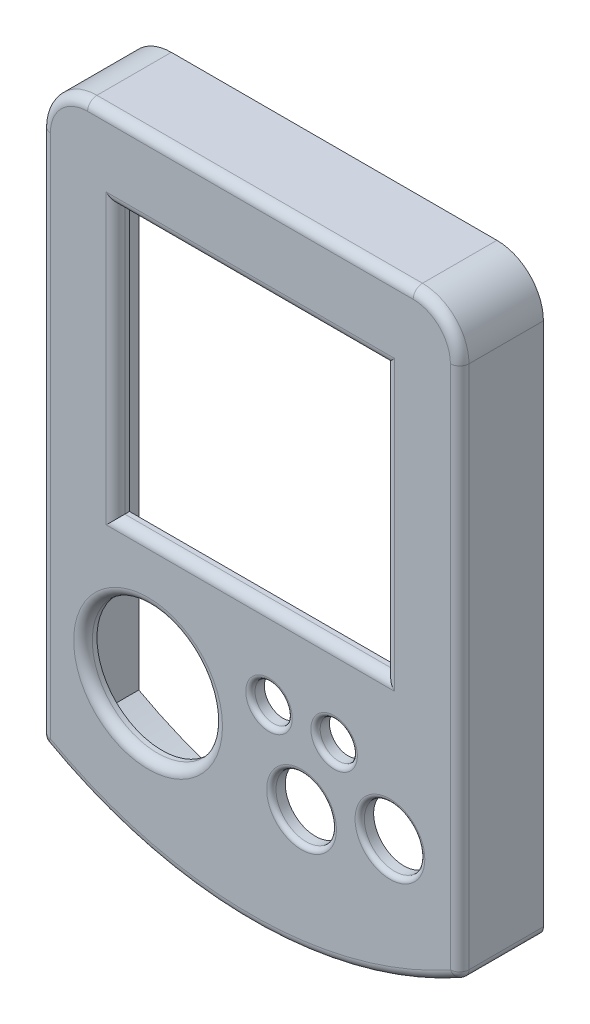
SolidWorks part; units mm, degrees
ref_plane "前视基准面" through (0, 0, 0) normal (0, 0, 1) x (1, 0, 0)
ref_plane "上视基准面" through (0, 0, 0) normal (0, 1, 0) x (1, 0, 0)
ref_plane "右视基准面" through (0, 0, 0) normal (1, 0, 0) x (0, 0, -1)
sketch "草图1" plane through (0, 0, 0) normal (0, 0, 1) x (1, 0, 0)
  line L1 (-40, 68) -> (-5, 68)
  line L2 (-45, 63) -> (-45, 0)
  line L3 (-45, 0) -> (0, 0)
  line L4 (0, 63) -> (0, 0)
  arc A0 (-5, 68) -> (0, 63) centre (-5, 63) cw
  arc A1 (-40, 68) -> (-45, 63) centre (-40, 63) ccw
  point P7 (0, 68)
  point P10 (-45, 68)
  dimension "D3" = 5
  dimension "D4" = 5
  dimension "D1" = 45
  dimension "D2" = 68
extrude "凸台-拉伸1" add sketch "草图1" along normal blind 9 contours L1 A0 L4 L3 L2 A1
sketch "草图3" plane through (0, 0, 0) normal (0, 0, -1) x (-1, 0, 0)
  line L0 (22.5, 0) -> (22.5, 50000) construction
  line L2 (0, 63) -> (0, 0) construction
  line L4 (45, 6) -> (45, 0)
  line L5 (45, 0) -> (0, 0)
  line L6 (0, 0) -> (0, 6)
  line L7 (0, 63) -> (0, 0) construction
  line L8 (45, 63) -> (45, 0) construction
  arc A0 (0, 6) -> (45, 6) centre (22.5, 45.1875) ccw
  point P7 (45, 6)
  line M3 (45, 0) -> (45, 63)
  line M5 (0, 63) -> (0, 0)
  line M6 (0, 0) -> (45, 0)
  dimension "D1" = 6
extrude "切除-拉伸2" cut sketch "草图3" against normal through all contours A0 L5 M3 | A0 M5 M6 region at (-5.5476, 1.7775, 0) region at (-39.4524, 1.7775, 0)
shell "抽壳2" thickness 1.5 removed face at (-22.5, 45.0118, 0)
sketch "草图4" plane through (0, 0, 0) normal (0, 0, -1) x (-1, 0, 0)
  line L0 (22.5, 68.5) -> (22.5, 50068.5) construction
  line L1 (8, 59.5) -> (37, 59.5)
  line L2 (8, 59.5) -> (8, 30.5)
  line L3 (8, 30.5) -> (37, 30.5)
  line L4 (37, 59.5) -> (37, 30.5)
  line L5 (40, 66.5) -> (5, 66.5) construction
  line L6 (40, 68) -> (5, 68) construction
  line L7 (45, 63) -> (45, 6) construction
  line L8 (0, 63) -> (0, 6) construction
  circle A0 centre (33.5, 17) radius 7
  circle A1 centre (7.5, 15.5) radius 3.25
  circle A2 centre (17, 13.5) radius 3.25
  circle A3 centre (13.5, 21.5) radius 2
  circle A4 centre (20.5, 21.5) radius 2
  point P8 (22.5, 66.5)
  point P25 (0, 0)
  dimension "D4" = 14
  dimension "D7" = 6.5
  dimension "D8" = 6.5
  dimension "D13" = 4
  dimension "D14" = 4
  dimension "D1" = 29
  dimension "D2" = 29
  dimension "D3" = 8.5
  dimension "D5" = 11.5
  dimension "D6" = 51
  dimension "D9" = 7.5
  dimension "D10" = 17
  dimension "D11" = 52.5
  dimension "D12" = 54.5
  dimension "D15" = 46.5
  dimension "D16" = 7
  dimension "D17" = 13.5
extrude "切除-拉伸3" cut sketch "草图4" against normal through all
fillet "圆角1" radius 1 4 edges at (-22.5, 59.5, 9) (-8, 45, 9) (-22.5, 30.5, 9) (-37, 45, 9)
fillet "圆角2" radius 1 1 edges at (-40.5, 17, 9)
fillet "圆角3" radius 0.5 4 edges at (-15.5, 21.5, 9) (-22.5, 21.5, 9) (-10.75, 15.5, 9) (-20.25, 13.5, 9)
fillet "圆角5" radius 1 2 edges at (0, 6, 4.5) (-45, 6, 4.5)
fillet "圆角7" radius 1 8 edges at (-0.1379, 6.0766, 9) (-44.8621, 6.0766, 9) (-22.5, 0, 9) (-45, 34.7916, 9) (-43.5355, 66.5355, 9) (0, 34.7916, 9) (-1.4645, 66.5355, 9) (-22.5, 68, 9)
